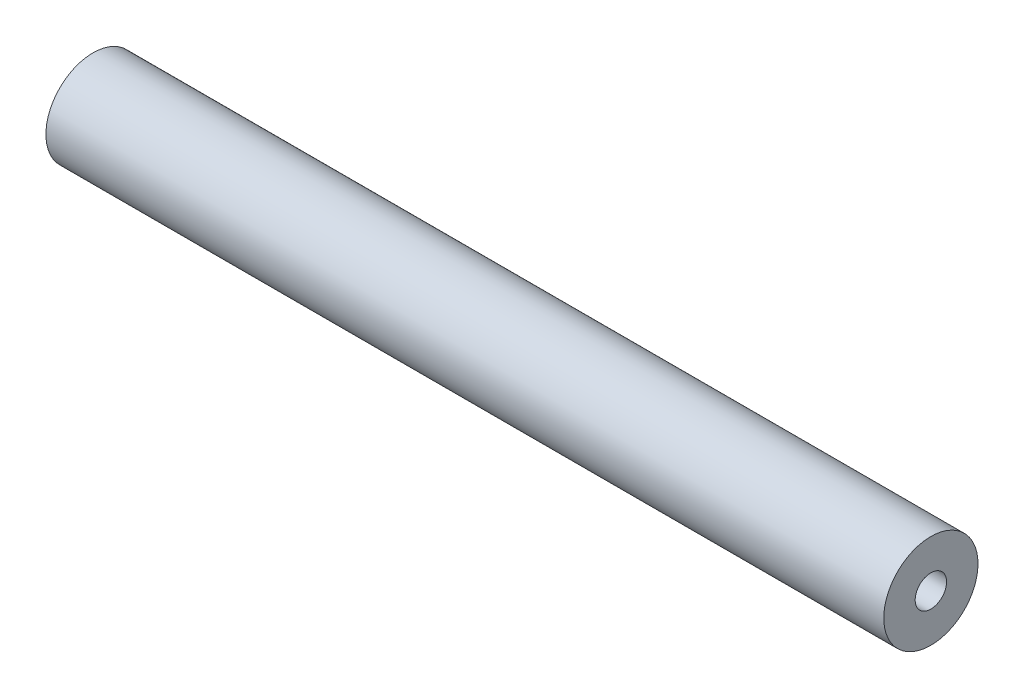
SolidWorks part; units mm, degrees
ref_plane "Ebene vorne" through (0, 0, 0) normal (0, 0, 1) x (1, 0, 0)
ref_plane "Ebene oben" through (0, 0, 0) normal (0, 1, 0) x (1, 0, 0)
ref_plane "Ebene rechts" through (0, 0, 0) normal (1, 0, 0) x (0, 0, -1)
sketch "Skizze1" plane through (0, 0, 0) normal (1, 0, 0) x (0, 0, -1)
  circle A0 centre (0, 0) radius 4.5
  dimension "D1" = 9
extrude "Aufsatz-Linear austragen1" add sketch "Skizze1" along normal blind 80
sketch "Skizze2" plane through (0, 0, 0) normal (-1, 0, 0) x (0, 0, 1)
  circle A0 centre (0, 0) radius 1.5
  dimension "D1" = 3
extrude "Schnitt-Linear austragen1" cut sketch "Skizze2" against normal blind 10
sketch "Skizze3" plane through (80, 0, 0) normal (1, 0, 0) x (0, 0, -1)
  circle A0 centre (0, 0) radius 1.5
  dimension "D1" = 3
extrude "Schnitt-Linear austragen2" cut sketch "Skizze3" against normal blind 10
